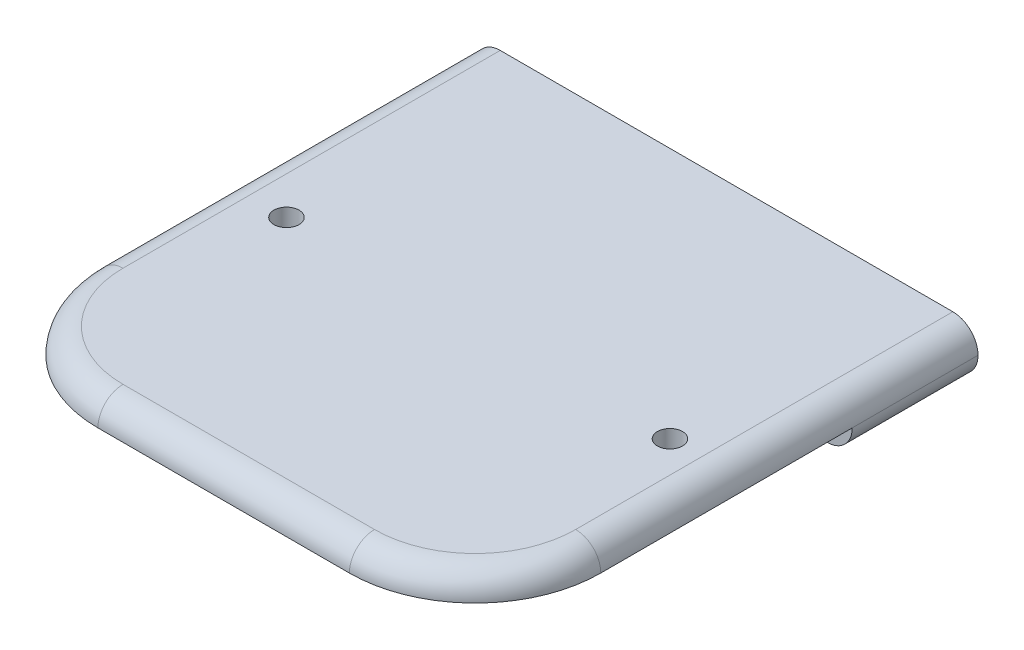
SolidWorks part; units mm, degrees
ref_plane "正面" through (0, 0, 0) normal (0, 0, 1) x (1, 0, 0)
ref_plane "平面" through (0, 0, 0) normal (0, 1, 0) x (1, 0, 0)
ref_plane "右側面" through (0, 0, 0) normal (1, 0, 0) x (0, 0, -1)
sketch "ｽｹｯﾁ1" plane through (0, 0, 0) normal (0, 0, 1) x (1, 0, 0)
  line L1 (0, 0) -> (40, 0)
  line L2 (0, 0) -> (0, 4)
  line L3 (0, 4) -> (40, 4)
  line L4 (40, 0) -> (40, 4)
  dimension "D1" = 40
  dimension "D2" = 4
extrude "ﾎﾞｽ - 押し出し1" add sketch "ｽｹｯﾁ1" along normal blind 40
sketch "ｽｹｯﾁ3" plane through (0, 0, 0) normal (0, -1, 0) x (1, 0, 0)
  line L0 (40, 40) -> (40, 0) construction
  line L1 (0, 40) -> (40, 40)
  line L2 (0, 40) -> (0, 10)
  line L3 (0, 10) -> (40, 10)
  line L4 (40, 40) -> (40, 10)
  dimension "D1" = 30
extrude "ｶｯﾄ - 押し出し1" cut sketch "ｽｹｯﾁ3" against normal blind 2
sketch "ｽｹｯﾁ4" plane through (0, 4, 0) normal (0, 1, 0) x (1, 0, 0)
  line L0 (40, -40) -> (0, -40) construction
  line L1 (40, -40) -> (40, 0) construction
  circle A0 centre (35.5, -20) radius 1
  dimension "D1" = 20
  dimension "D2" = 4.5
extrude "ｶｯﾄ - 押し出し2" cut sketch "ｽｹｯﾁ4" against normal blind 4
sketch "ｽｹｯﾁ6" plane through (0, 4, 0) normal (0, 1, 0) x (1, 0, 0)
  line L0 (40, -40) -> (0, -40) construction
  line L1 (0, -40) -> (0, 0) construction
  circle A0 centre (5, -20) radius 1
  dimension "D1" = 20
  dimension "D2" = 5
extrude "ｶｯﾄ - 押し出し3" cut sketch "ｽｹｯﾁ6" against normal blind 4
fillet "ﾌｨﾚｯﾄ4" radius 10 1 edges at (40, 3, 40)
fillet "ﾌｨﾚｯﾄ5" radius 10 1 edges at (0, 3, 40)
fillet "ﾌｨﾚｯﾄ6" radius 2 5 edges at (0, 4, 15) (2.9289, 4, 37.0711) (20, 4, 40) (37.0711, 4, 37.0711) (40, 4, 15)
fillet "ﾌｨﾚｯﾄ7" radius 2 1 edges at (40, 0, 5)
fillet "ﾌｨﾚｯﾄ8" radius 2 1 edges at (0, 0, 5)
